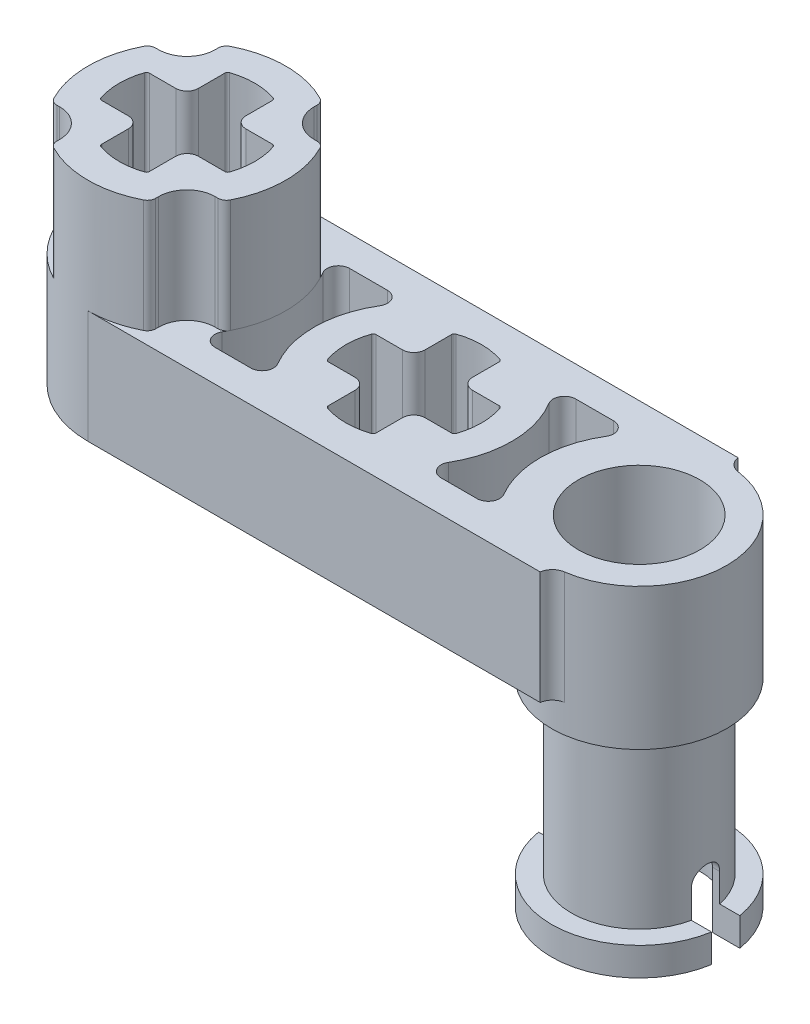
SolidWorks part; units mm, degrees
ref_plane "Front Plane" through (0, 0, 0) normal (0, 0, 1) x (1, 0, 0)
ref_plane "Top Plane" through (0, 0, 0) normal (0, 1, 0) x (1, 0, 0)
ref_plane "Right Plane" through (0, 0, 0) normal (1, 0, 0) x (0, 0, -1)
sketch "Sketch2" plane through (0, 0, 0) normal (0, 1, 0) x (1, 0, 0)
  line L0 (0, 0) -> (16, 0) construction
  line L1 (0, 3.5) -> (16, 3.5)
  line L2 (0, -3.5) -> (16, -3.5)
  arc A0 (0, 3.5) -> (0, -3.5) centre (0, 0) ccw
  arc A1 (16, -3.5) -> (16, 3.5) centre (16, 0) ccw
  point P3 (8, 0)
  point P8 (-3.5, 0)
  point P9 (19.5, 0)
  point P10 (0, 0)
  point P11 (0, 0)
  dimension "D1" = 23
  dimension "D2" = 7
extrude "Boss-Extrude1" add sketch "Sketch2" along normal mid plane 4
sketch "Sketch3" plane through (0, 2, 0) normal (0, 1, 0) x (1, 0, 0)
  line L0 (1.75, 2.75) -> (1.75, 2.8526)
  line L2 (-1.75, -2.8526) -> (-1.75, -2.75)
  line L4 (1.75, -2.8526) -> (1.75, -2.75)
  line L6 (2.75, -1.75) -> (2.8526, -1.75)
  line L7 (-2.8526, 1.75) -> (-2.75, 1.75)
  line L9 (-2.8526, -1.75) -> (-2.75, -1.75)
  line L16 (2.75, 1.75) -> (2.8526, 1.75)
  line L17 (-1.75, 2.75) -> (-1.75, 2.8526)
  arc A0 (1.5859, 3.1201) -> (-1.5859, 3.1201) centre (0, 0) ccw
  arc A1 (3.1201, -1.5859) -> (3.1201, 1.5859) centre (0, 0) ccw
  arc A2 (-3.1201, 1.5859) -> (-3.1201, -1.5859) centre (0, 0) ccw
  arc A3 (-1.5859, -3.1201) -> (1.5859, -3.1201) centre (0, 0) ccw
  arc A4 (1.75, 2.75) -> (2.75, 1.75) centre (2.75, 2.75) ccw
  arc A5 (2.75, -1.75) -> (1.75, -2.75) centre (2.75, -2.75) ccw
  arc A6 (-1.75, -2.75) -> (-2.75, -1.75) centre (-2.75, -2.75) ccw
  arc A7 (-1.75, 2.75) -> (-2.75, 1.75) centre (-2.75, 2.75) cw
  arc A8 (-3.1201, -1.5859) -> (-2.8526, -1.75) centre (-2.8526, -1.45) ccw
  arc A9 (1.5859, -3.1201) -> (1.75, -2.8526) centre (1.45, -2.8526) ccw
  arc A10 (-1.5859, -3.1201) -> (-1.75, -2.8526) centre (-1.45, -2.8526) cw
  arc A11 (3.1201, -1.5859) -> (2.8526, -1.75) centre (2.8526, -1.45) cw
  arc A12 (2.8526, 1.75) -> (3.1201, 1.5859) centre (2.8526, 1.45) cw
  arc A13 (1.5859, 3.1201) -> (1.75, 2.8526) centre (1.45, 2.8526) cw
  arc A14 (-1.5859, 3.1201) -> (-1.75, 2.8526) centre (-1.45, 2.8526) ccw
  arc A15 (-2.8526, 1.75) -> (-3.1201, 1.5859) centre (-2.8526, 1.45) ccw
  point P15 (1.75, 1.75)
  point P32 (3.0311, -1.75)
  point P35 (3.0311, 1.75)
  point P38 (1.75, 3.0311)
  point P41 (-1.75, 3.0311)
  dimension "D3" = 1
  dimension "D4" = 0.3
  dimension "D1" = 3.5
  dimension "D2" = 3.5
extrude "Boss-Extrude3" add sketch "Sketch3" along normal blind 4
sketch "Sketch4" plane through (0, 6, 0) normal (0, 1, 0) x (1, 0, 0)
  line L0 (-0.8615, -1.2125) -> (-0.8615, -2.1502)
  line L1 (-0.8615, 2.2052) -> (-0.8615, 1.2675)
  line L2 (0.8185, 2.2052) -> (0.8185, 1.2675)
  line L3 (-0.8615, 2.2757) -> (0.8185, -2.2207) construction
  line L4 (-0.8615, -2.2207) -> (0.8185, 2.2757) construction
  line L5 (-2.1993, 0.8675) -> (-1.2615, 0.8675)
  line L6 (-2.1993, -0.8125) -> (-1.2615, -0.8125)
  line L7 (-2.2697, 0.8675) -> (2.2267, -0.8125) construction
  line L8 (-2.2697, -0.8125) -> (2.2267, 0.8675) construction
  line L9 (1.2185, 0.8675) -> (2.1562, 0.8675)
  line L10 (0.8185, -1.2125) -> (0.8185, -2.1502)
  line L11 (1.2185, -0.8125) -> (2.1562, -0.8125)
  arc A1 (0.7506, 2.2999) -> (-0.7937, 2.2999) centre (-0.0215, 0.0275) ccw
  arc A2 (-2.2939, 0.7997) -> (-2.2939, -0.7447) centre (-0.0215, 0.0275) ccw
  arc A3 (2.2508, -0.7447) -> (2.2508, 0.7997) centre (-0.0215, 0.0275) ccw
  arc A4 (-0.7937, -2.2449) -> (0.7506, -2.2449) centre (-0.0215, 0.0275) ccw
  arc A5 (-2.1993, 0.8675) -> (-2.2939, 0.7997) centre (-2.1993, 0.7675) ccw
  arc A6 (-2.2939, -0.7447) -> (-2.1993, -0.8125) centre (-2.1993, -0.7125) ccw
  arc A7 (-0.8615, -2.1502) -> (-0.7937, -2.2449) centre (-0.7615, -2.1502) ccw
  arc A8 (0.7506, -2.2449) -> (0.8185, -2.1502) centre (0.7185, -2.1502) ccw
  arc A9 (2.1562, -0.8125) -> (2.2508, -0.7447) centre (2.1562, -0.7125) ccw
  arc A10 (2.1562, 0.8675) -> (2.2508, 0.7997) centre (2.1562, 0.7675) cw
  arc A11 (0.7506, 2.2999) -> (0.8185, 2.2052) centre (0.7185, 2.2052) cw
  arc A12 (-0.7937, 2.2999) -> (-0.8615, 2.2052) centre (-0.7615, 2.2052) ccw
  arc A13 (-0.8615, -1.2125) -> (-1.2615, -0.8125) centre (-1.2615, -1.2125) ccw
  arc A14 (0.8185, -1.2125) -> (1.2185, -0.8125) centre (1.2185, -1.2125) cw
  arc A15 (1.2185, 0.8675) -> (0.8185, 1.2675) centre (1.2185, 1.2675) cw
  arc A16 (-1.2615, 0.8675) -> (-0.8615, 1.2675) centre (-1.2615, 1.2675) ccw
  point P3 (0, 0)
extrude "Cut-Extrude1" cut sketch "Sketch4" against normal through all
sketch "Sketch8" plane through (0, 2, 0) normal (0, 1, 0) x (1, 0, 0)
  circle A0 centre (16, 0) radius 2.15
  dimension "D1" = 4.3
extrude "Cut-Extrude3" cut sketch "Sketch8" against normal blind 4
sketch "Sketch10" plane through (0, -2, 0) normal (0, -1, 0) x (-1, 0, 0)
  circle A0 centre (-16, 0) radius 3.1
  dimension "D1" = 6.2
extrude "Boss-Extrude4" add sketch "Sketch10" along normal blind 1
sketch "Sketch12" plane through (0, -2, 0) normal (0, -1, 0) x (-1, 0, 0)
  circle A0 centre (-16, 0) radius 2.4
  dimension "D1" = 4.8
extrude "Boss-Extrude5" add sketch "Sketch12" along normal blind 7
sketch "Sketch15" plane through (0, -9, 0) normal (0, -1, 0) x (-1, 0, 0)
  circle A0 centre (-16, 0) radius 3.1
  dimension "D1" = 6.2
extrude "Boss-Extrude6" add sketch "Sketch15" along normal blind 1
sketch "Sketch16" plane through (0, -2, 0) normal (0, 1, 0) x (1, 0, 0)
  circle A0 centre (16, 0) radius 2.15
  dimension "D1" = 4.3
extrude "Cut-Extrude4" cut sketch "Sketch16" against normal through all
sketch "Sketch17" plane through (0, 0, 0) normal (1, 0, 0) x (0, 0, -1)
  line L0 (0, -10) -> (0, -8) construction
  line L1 (-3.1, -10) -> (3.1, -10) construction
  line L2 (-0.5, -10) -> (-0.5, -8)
  line L3 (0.5, -10) -> (0.5, -8)
  arc A0 (-0.5, -10) -> (0.5, -10) centre (0, -10) ccw
  arc A1 (0.5, -8) -> (-0.5, -8) centre (0, -8) ccw
  point P5 (0, -9)
  point P10 (0, -7.5)
  point P11 (0, -10.5)
  dimension "D1" = 1
  dimension "D2" = 3
extrude "Cut-Extrude5" cut sketch "Sketch17" against normal through all both and the other way through all
pattern_linear "LPattern3" count 2 spacing 8.02 along (1, 0, 0) of "Cut-Extrude1"
sketch "Sketch20" plane through (0, 2, 0) normal (0, 1, 0) x (1, 0, 0)
  line L0 (11.33, 2.4275) -> (12.6684, 2.4275)
  line L1 (11.3629, -2.3725) -> (12.6356, -2.3725)
  arc A0 (13.0101, 1.8195) -> (12.9807, -1.7702) centre (16, 0) ccw
  arc A1 (11.0178, -1.7702) -> (10.9883, 1.8195) centre (7.9985, 0) ccw
  arc A4 (11.0178, -1.7702) -> (11.3629, -2.3725) centre (11.3629, -1.9725) ccw
  arc A5 (12.9807, -1.7702) -> (12.6356, -2.3725) centre (12.6356, -1.9725) cw
  arc A6 (13.0101, 1.8195) -> (12.6684, 2.4275) centre (12.6684, 2.0275) ccw
  arc A7 (11.33, 2.4275) -> (10.9883, 1.8195) centre (11.33, 2.0275) ccw
  dimension "D1" = 7
  dimension "D2" = 7
  dimension "D3" = 0.4
extrude "Cut-Extrude6" cut sketch "Sketch20" against normal through all
pattern_linear "LPattern4" count 2 spacing 8 along (-1, 0, 0) of "Cut-Extrude6"
sketch "Sketch25" plane through (0, 2, 0) normal (0, 1, 0) x (1, 0, 0)
  line L0 (16, 3.5) -> (16, 3.1)
  line L1 (16, -3.5) -> (16, -3.1)
  arc A0 (16, 3.1) -> (16, -3.1) centre (16, 0) cw
  arc A1 (16, 3.5) -> (16, -3.5) centre (16, 0) cw
extrude "Cut-Extrude7" cut sketch "Sketch25" against normal through all
fillet "Fillet2" radius 0.5 1 edges at (16, 0, 3.1)
fillet "Fillet3" radius 0.5 1 edges at (16, 0, -3.1)
